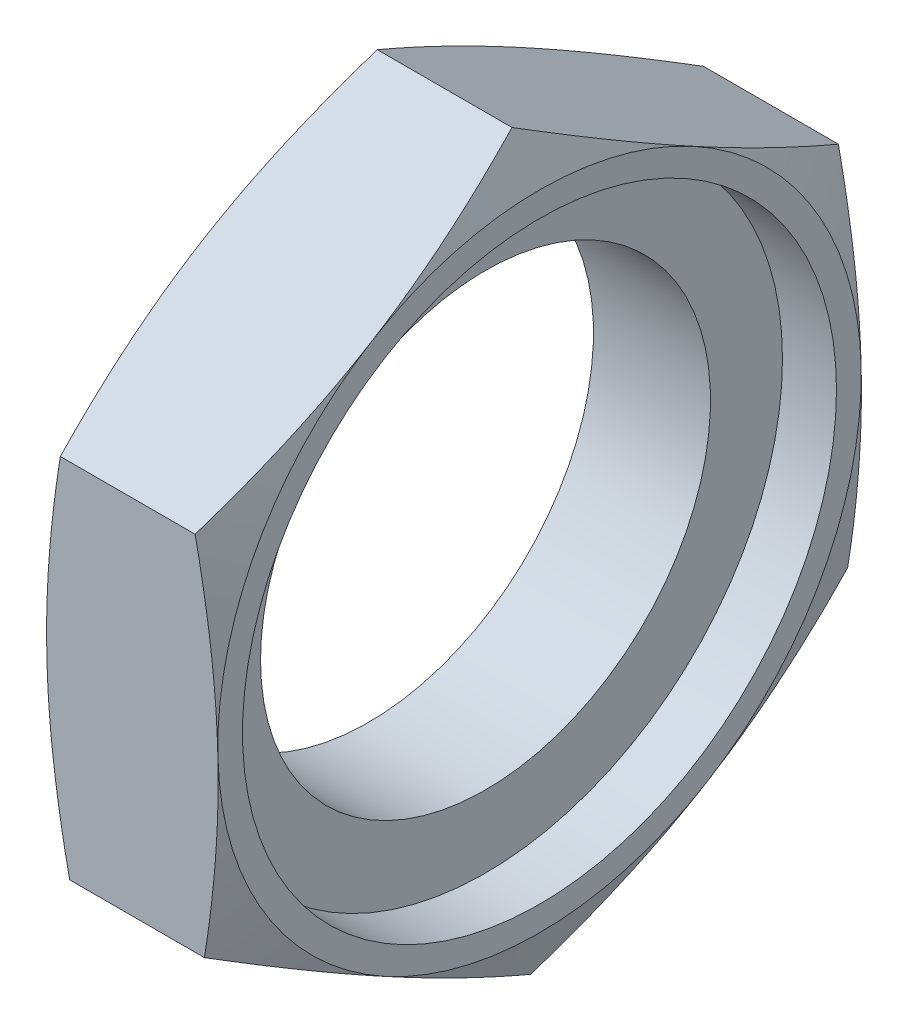
SolidWorks part; units mm, degrees
material "AISI 1020"
ref_plane "Plano superior" through (0, 0, 0) normal (0, 0, 1) x (1, 0, 0)
ref_plane "Plano frontal" through (0, 0, 0) normal (0, 1, 0) x (1, 0, 0)
ref_plane "Plano direito" through (0, 0, 0) normal (1, 0, 0) x (0, 0, -1)
sketch "Esboço1" plane through (0, 0, 0) normal (1, 0, 0) x (0, 0, -1)
  line L1 (14.0875, 8.6137) -> (-0.416, 16.507)
  line L2 (-0.416, 16.507) -> (-14.5034, 7.8932)
  line L3 (-14.5034, 7.8932) -> (-14.0875, -8.6137)
  line L4 (-14.0875, -8.6137) -> (0.416, -16.507)
  line L5 (0.416, -16.507) -> (14.5034, -7.8932)
  line L6 (14.5034, -7.8932) -> (14.0875, 8.6137)
  circle A0 centre (0, 0) radius 14.3 construction
  circle A1 centre (0, 0) radius 10
  dimension "D1" = 28.6
  dimension "D2" = 20
extrude "Ressalto-extrusão1" add sketch "Esboço1" along normal blind 7.6
cosmetic thread "Representação de rosca2" parameters "D2"=22
sketch "Esboço3" plane through (0, 0, 0) normal (-1, 0, 0) x (0, 0, 1)
  circle A0 centre (0, 0) radius 14.3
sketch "Esboço4" plane through (7.6, 0, 0) normal (1, 0, 0) x (0, 0, -1)
  circle A0 centre (0, 0) radius 14.3
hole_wizard "Furo1" positions "Esboço5" profile "Esboço6" legacy
sketch "Esboço5" plane through (7.6, 0, 0) normal (1, 0, 0) x (0, 0, -1)
  point P0 (0, 0)
  point P3 (0, 0)
sketch "Esboço6" plane through (7.6, 0, 0) normal (0, 1, 0) x (0, 0, -1)
  line L0 (0, 0) -> (0, 2.4)
  line L1 (0, 2.4) -> (13.2, 2.4)
  line L2 (13.2, 2.4) -> (13.2, 0)
  line L3 (13.2, 0) -> (0, 0)
  line L4 (0, 110) -> (0, -10) construction
  dimension "Diameter" = 26.4
  dimension "Depth" = 2.4
sketch "Esboço7" plane through (7.6, 0, 0) normal (1, 0, 0) x (0, 0, -1)
  circle A0 centre (0, 0) radius 14.3
extrude "Corte-extrusão1" cut sketch "Esboço7" against normal blind 13 draft 70 flip side to cut
sketch "Esboço8" plane through (0, 0, 0) normal (-1, 0, 0) x (0, 0, 1)
  circle A0 centre (0, 0) radius 14.3
extrude "Corte-extrusão2" cut sketch "Esboço8" against normal blind 13 draft 70 flip side to cut
ref_axis "Eixo1" through (-0.38, 0, 0) along (1, 0, 0)
